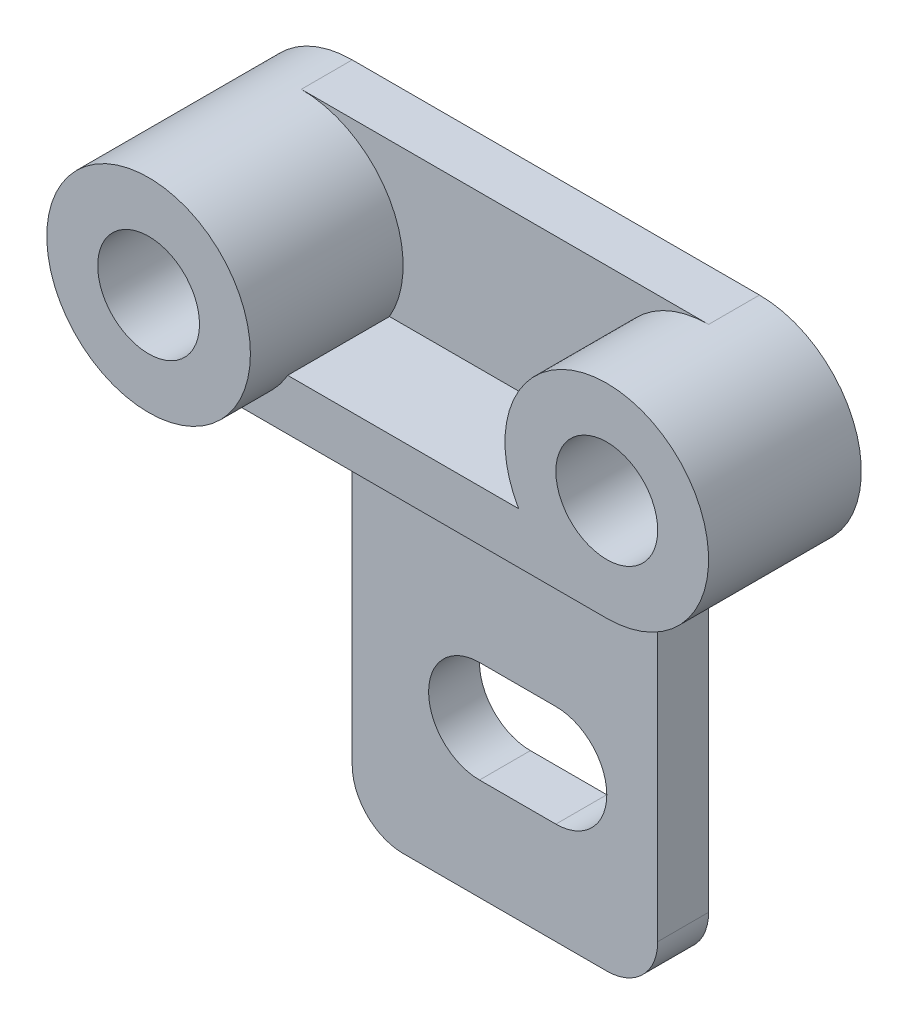
SolidWorks part; units mm, degrees
ref_plane "Front Plane" through (0, 0, 0) normal (0, 0, 1) x (1, 0, 0)
ref_plane "Top Plane" through (0, 0, 0) normal (0, 1, 0) x (1, 0, 0)
ref_plane "Right Plane" through (0, 0, 0) normal (1, 0, 0) x (0, 0, -1)
sketch "Sketch1" plane through (0, 0, 0) normal (0, 0, 1) x (1, 0, 0)
  line L1 (20, 40) -> (100, 40)
  line L3 (100, 0) -> (20, 0)
  line L4 (60, -3.6615) -> (60, 55.7509) construction
  line L8 (0, 0) -> (0, 58.3288) construction
  line L9 (82.6795, 10) -> (37.3205, 10)
  line L10 (30, 0) -> (30, -70)
  line L11 (40, -80) -> (80, -80)
  line L12 (90, -70) -> (90, 0)
  line L13 (55, -50) -> (70, -50) construction
  line L14 (55, -40) -> (70, -40)
  line L15 (55, -60) -> (70, -60)
  circle A0 centre (20, 20) radius 10
  circle A1 centre (20, 20) radius 20
  circle A2 centre (100, 20) radius 10
  arc A3 (82.6795, 10) -> (100, 0) centre (100, 20) cw
  arc A4 (80, -80) -> (90, -70) centre (80, -70) ccw
  arc A5 (30, -70) -> (40, -80) centre (40, -70) ccw
  arc A6 (55, -40) -> (55, -60) centre (55, -50) ccw
  arc A7 (70, -60) -> (70, -40) centre (70, -50) ccw
  point P20 (90, -80)
  point P25 (30, -80)
  point P28 (62.5, -50)
  point P33 (0, 0)
  point P34 (0, 0)
  point P35 (106.9237, -56.7208)
  dimension "D3" = 20
  dimension "D4" = 40
  dimension "D10" = 10
  dimension "D12" = 10
  dimension "D1" = 40
  dimension "D2" = 10
  dimension "D5" = 80
  dimension "D6" = 40
  dimension "D7" = 30
  dimension "D8" = 60
  dimension "D9" = 80
  dimension "D11" = 15
  dimension "D13" = 20
  dimension "D14" = 30
extrude "Boss-Extrude1" add sketch "Sketch1" along normal blind 10 contours A1 A0 | L9 A3 L1 A1 | A3 L9 A1 L3 A2 region at (60, 26.1452, 0) region at (33.7421, 33.7421, 0) region at (85.1864, 14.2972, 0)
extrude "Boss-Extrude2" add sketch "Sketch1<4>" along normal blind 40 contours A1
sketch "Sketch1<4>" plane through (0, 0, 0) normal (0, 0, 1) x (1, 0, 0) same geometry as "Sketch1"
extrude "Cut-Extrude1" cut sketch "Sketch1<5>" along normal through all contours A0
sketch "Sketch1<5>" plane through (0, 0, 0) normal (0, 0, 1) x (1, 0, 0) same geometry as "Sketch1"
extrude "Boss-Extrude3" add sketch "Sketch1<10>" along normal blind 30 separate body contours A3 L9 A1 L3 A2 | A2 region at (85.1864, 14.2972, 0)
sketch "Sketch1<10>" plane through (0, 0, 0) normal (0, 0, 1) x (1, 0, 0) same geometry as "Sketch1"
extrude "Cut-Extrude2" cut sketch "Sketch1<11>" along normal through all contours A2
sketch "Sketch1<11>" plane through (0, 0, 0) normal (0, 0, 1) x (1, 0, 0) same geometry as "Sketch1"
extrude "Boss-Extrude4" add sketch "Sketch1<13>" along normal blind 10 separate body contours L10 A5 L11 A4 L12 L3 A7 L15 A6 L14 region at (59.6294, -38.1263, 0)
sketch "Sketch1<13>" plane through (0, 0, 0) normal (0, 0, 1) x (1, 0, 0) same geometry as "Sketch1"
